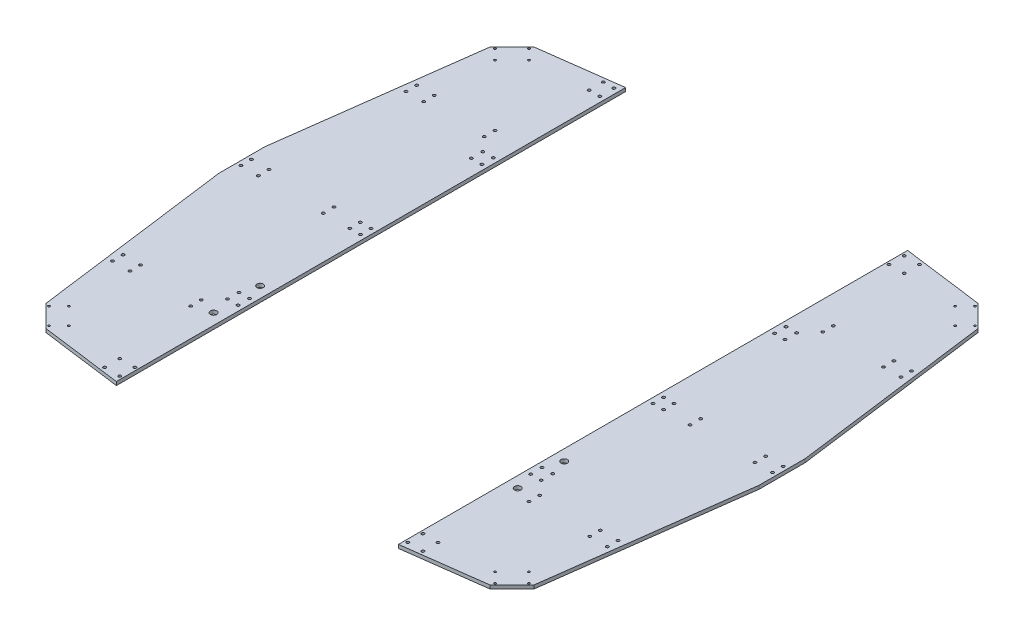
SolidWorks part; units mm, degrees
ref_plane "前视基准面" through (0, 0, 0) normal (0, 0, 1) x (1, 0, 0)
ref_plane "上视基准面" through (0, 0, 0) normal (0, 1, 0) x (1, 0, 0)
ref_plane "右视基准面" through (0, 0, 0) normal (1, 0, 0) x (0, 0, -1)
other "Configuration Table"
sketch "草图1" plane through (0, 0, 0) normal (0, 1, 0) x (1, 0, 0)
  line L0 (-314.9222, 345.9222) -> (-345.9222, 314.9222)
  line L5 (325, -325) -> (-325, 325) construction
  line L6 (325, 325) -> (-325, -325) construction
  line L7 (0, 325) -> (0, -325) construction
  line L8 (-383.07, 0) -> (383.0748, 0) construction
  line L9 (314.9222, 345.9222) -> (32.7201, 383.0748)
  line L10 (314.9222, 345.9222) -> (345.9222, 314.9222)
  line L11 (-383.07, 13.0001) -> (-230, 13.0001) construction
  line L12 (-314.9222, 345.9222) -> (-32.7201, 383.0748)
  line L13 (0, 325) -> (0, 399.6983)
  line L14 (-32.7201, 383.0748) -> (32.7201, 383.0748)
  line L15 (314.9222, -345.9222) -> (32.7201, -383.0748)
  line L16 (-32.7201, -383.0748) -> (32.7201, -383.0748)
  line L17 (-314.9222, -345.9222) -> (-32.7201, -383.0748)
  line L18 (-314.9222, -345.9222) -> (-345.9222, -314.9222)
  line L19 (-345.9222, 314.9222) -> (-383.0748, 32.7201)
  line L20 (-383.0748, -32.7201) -> (-383.0748, 32.7201)
  line L21 (-345.9222, -314.9222) -> (-383.0748, -32.7201)
  line L22 (-345.9222, -314.9222) -> (-314.9222, -345.9222)
  line L23 (345.9222, -314.9222) -> (314.9222, -345.9222)
  line L24 (345.9222, -314.9222) -> (383.0748, -32.7201)
  line L25 (383.0748, 32.7201) -> (383.0748, -32.7201)
  line L26 (345.9222, 314.9222) -> (383.0748, 32.7201)
  line L27 (-383.07, -12.9999) -> (-230, -12.9999) construction
  line L29 (361.6863, 195.182) -> (230, 195.182) construction
  line L30 (358.2633, 221.182) -> (230, 221.182) construction
  line L31 (-358.2633, 221.182) -> (-230, 221.182) construction
  line L32 (-361.6863, 195.182) -> (-230, 195.182) construction
  line L33 (361.6863, -195.182) -> (230, -195.182) construction
  line L34 (358.2633, -221.182) -> (230, -221.182) construction
  line L35 (-361.6863, -195.182) -> (-230, -195.182) construction
  line L36 (-358.2633, -221.182) -> (-230, -221.182) construction
  line L37 (-228, -357.3657) -> (-228, 357.3618) construction
  line L38 (-202, -360.7887) -> (-202, 360.7847) construction
  line L39 (383.07, 13.0001) -> (230, 13.0001) construction
  circle A5 centre (0, 0) radius 250
  circle A6 centre (302.1379, 326.1795) radius 1.5
  circle A7 centre (316.28, 340.3217) radius 1.5
  circle A8 centre (340.3217, 316.28) radius 1.5
  circle A9 centre (326.1795, 302.1379) radius 1.5
  circle A10 centre (302.1379, -326.1795) radius 1.5
  circle A11 centre (316.28, -340.3217) radius 1.5
  circle A12 centre (326.1795, -302.1379) radius 1.5
  circle A13 centre (340.3217, -316.28) radius 1.5
  circle A14 centre (-326.1795, -302.1379) radius 1.5
  circle A15 centre (-340.3217, -316.28) radius 1.5
  circle A16 centre (-302.1379, -326.1795) radius 1.5
  circle A17 centre (-316.28, -340.3217) radius 1.5
  circle A18 centre (-302.1379, 326.1795) radius 1.5
  circle A19 centre (-316.28, 340.3217) radius 1.5
  circle A20 centre (-326.1795, 302.1379) radius 1.5
  circle A21 centre (-340.3217, 316.28) radius 1.5
  circle A22 centre (350.9184, 215.682) radius 2
  circle A23 centre (377.0748, 7.5001) radius 2
  circle A24 centre (350.9184, 200.682) radius 2
  circle A25 centre (325.9184, 215.682) radius 2
  circle A26 centre (325.9184, 200.682) radius 2
  circle A27 centre (377.0748, -7.5951) radius 2
  circle A28 centre (352.0748, 7.5001) radius 2
  circle A29 centre (352.0748, -7.5951) radius 2
  circle A30 centre (350.9184, -200.682) radius 2
  circle A31 centre (350.9184, -215.682) radius 2
  circle A32 centre (325.9184, -200.682) radius 2
  circle A33 centre (325.9184, -215.682) radius 2
  circle A34 centre (-350.9184, -200.682) radius 2
  circle A35 centre (-325.9184, -200.682) radius 2
  circle A36 centre (-350.9184, -215.682) radius 2
  circle A37 centre (-325.9184, -215.682) radius 2
  circle A38 centre (-377.0748, 7.5001) radius 2
  circle A39 centre (-352.0748, 7.5001) radius 2
  circle A40 centre (-377.0748, -7.4999) radius 2
  circle A41 centre (-352.0748, -7.4999) radius 2
  circle A42 centre (-350.9184, 215.682) radius 2
  circle A43 centre (-350.9184, 200.682) radius 2
  circle A44 centre (-325.9184, 215.682) radius 2
  circle A45 centre (-325.9184, 200.682) radius 2
  circle A46 centre (-222.5, -164.8255) radius 2
  circle A47 centre (-207.5, -164.8255) radius 2
  circle A48 centre (-222.5, -181.0301) radius 2
  circle A49 centre (-207.5, -181.0301) radius 2
  circle A50 centre (-222.5, 181.0301) radius 2
  circle A51 centre (-207.5, 164.8255) radius 2
  circle A52 centre (-222.5, 164.8255) radius 2
  circle A53 centre (-207.5, 181.0301) radius 2
  circle A54 centre (207.5, -164.8255) radius 2
  circle A55 centre (222.5, -164.8255) radius 2
  circle A56 centre (207.5, -181.0301) radius 2
  circle A57 centre (222.5, -181.0301) radius 2
  circle A58 centre (207.5, 164.8255) radius 2
  circle A59 centre (222.5, 164.8255) radius 2
  circle A60 centre (207.5, 181.0301) radius 2
  circle A61 centre (222.5, 181.0301) radius 2
  circle A62 centre (-240, 215.682) radius 2
  circle A63 centre (-240, 200.682) radius 2
  circle A64 centre (-260, 7.5) radius 2
  circle A65 centre (-260, -7.5) radius 2
  circle A66 centre (-240, -200.682) radius 2
  circle A67 centre (-240, -215.682) radius 2
  circle A68 centre (240, -215.682) radius 2
  circle A69 centre (240, -200.682) radius 2
  circle A72 centre (240, 200.682) radius 2
  circle A73 centre (240, 215.682) radius 2
  circle A74 centre (207.5, 9.4052) radius 2
  circle A75 centre (222.5, 9.4052) radius 2
  circle A76 centre (207.5, -5.5948) radius 2
  circle A77 centre (222.5, -5.5948) radius 2
  circle A78 centre (-222.5, -5.5948) radius 2
  circle A79 centre (-207.5, -5.5948) radius 2
  circle A80 centre (-222.5, 9.4052) radius 2
  circle A81 centre (-207.5, 9.4052) radius 2
  circle A82 centre (260, -7.5) radius 2
  circle A83 centre (260, 7.5) radius 2
  circle A84 centre (215.6127, -141.5543) radius 4.5
  circle A85 centre (215.6127, -207.5543) radius 4.5
  circle A86 centre (-215.6127, -207.5543) radius 4.5
  circle A87 centre (-215.6127, -141.5543) radius 4.5
  point P0 (0, 0)
  point P13 (0, 383.0748)
  point P24 (-330.4222, -330.4222)
  point P75 (0, 0)
  dimension "D6" = 25
  dimension "D7" = 15
  dimension "D8" = 500
  dimension "D5" = 4
  dimension "D13" = 6
  dimension "D14" = 6
  dimension "D15" = 6
  dimension "D16" = 6
  dimension "D17" = 25
  dimension "D20" = 8
  dimension "D21" = 25
  dimension "D23" = 8
  dimension "D28" = 5.5
  dimension "D29" = 5.5
  dimension "D30" = 5.5
  dimension "D31" = 5.5
  dimension "D32" = 5.5
  dimension "D33" = 5.5
  dimension "D35" = 5.5
  dimension "D37" = 5.5
  dimension "D1" = 650
  dimension "D2" = 650
  dimension "D3" = 31
  dimension "D4" = 142.5
  dimension "D9" = 5.5
  dimension "D10" = 5.5
  dimension "D11" = 25
  dimension "D12" = 25
  dimension "D22" = 25
  dimension "D24" = 25
  dimension "D25" = 25
  dimension "D26" = 25
  dimension "D27" = 5.5
  dimension "D34" = 5.5
  dimension "D36" = 5.5
  dimension "D38" = 7.5001
  dimension "D39" = 7.4999
  dimension "D40" = 7.5
  dimension "D41" = 7.5
extrude "凸台-拉伸2" add sketch "草图1" along normal blind 5 contours L26 L10 L9 L14 L12 L0 L19 L20 L21 L18 L17 L16 L15 L23 L24 L25 | A13 L22 | L22 | A13 L18 region at (-172.4069, 0, -353.7562)
sketch "草图2" plane through (0, 5, 0) normal (0, 1, 0) x (1, 0, 0)
  line L0 (0, 0) -> (-330.4222, -330.4222) construction
  line L1 (0, 383.0748) -> (0, -383.0748)
  line L2 (-32.7201, 383.0748) -> (32.7201, 383.0748) construction
  line L3 (-32.7201, -383.0748) -> (32.7201, -383.0748) construction
  line L4 (-200, 361.052) -> (-200, -361.052)
  line L5 (-314.9222, 345.9222) -> (-32.7201, 383.0748) construction
  line L6 (-314.9222, -345.9222) -> (-32.7201, -383.0748) construction
  line L7 (200, 361.052) -> (200, -361.052)
  line L8 (314.9222, 345.9222) -> (32.7201, 383.0748) construction
  line L9 (314.9222, -345.9222) -> (32.7201, -383.0748) construction
  line L10 (-200, 361.052) -> (-200, 484.7149)
  line L11 (-200, 484.7149) -> (200, 484.7149)
  line L12 (200, 484.7149) -> (200, 361.052)
  line L13 (-200, -361.052) -> (-200, -418.819)
  line L14 (-200, -418.819) -> (200, -418.819)
  line L15 (200, -418.819) -> (200, -361.052)
  dimension "D1" = 200
  dimension "D2" = 200
extrude "切除-拉伸1" cut sketch "草图2" against normal blind 122 and the other way through all contours L4 L1 | L7 L1 | L7 L1 | L4 L1 | L0 L4 region at (-190.1188, 5, -422.8834)
sketch "草图3" plane through (0, 0, 0) normal (0, -1, 0) x (-1, 0, 0)
  circle A0 centre (225.7527, -352.0225) radius 2
  circle A1 centre (204.2473, -352.0225) radius 2
  circle A2 centre (225.7527, -330.517) radius 2
  circle A3 centre (204.2473, -330.517) radius 2
extrude "切除-拉伸2" cut sketch "草图3" along normal through all and the other way blind 39 contours A0 | A1 | A2 | A3
sketch "草图4" plane through (0, 5, 0) normal (0, 1, 0) x (1, 0, 0)
  line L0 (-222.5, 352.0186) -> (-207.5, 352.0186)
  line L1 (-215, 352.0186) -> (-215, 337.3883)
  line L2 (-228, -357.3657) -> (-228, 357.3618) construction
  line L3 (-202, -360.7887) -> (-202, 360.7847) construction
  line L4 (-228, -357.3657) -> (-228, 357.3618)
  line L5 (-202, -360.7887) -> (-202, 360.7847)
  line L6 (-202, 337.3883) -> (-228, 337.3883)
  circle A0 centre (-222.5, 352.0186) radius 2
  circle A1 centre (-207.5, 352.0186) radius 2
  circle A2 centre (-222.5, 332.0186) radius 2
  circle A3 centre (-207.5, 332.0186) radius 2
  circle A4 centre (204.2473, 330.5131) radius 2
  circle A5 centre (225.7527, 330.5131) radius 2
  circle A6 centre (204.2473, 352.0186) radius 2
  circle A7 centre (225.7527, 352.0186) radius 2
  circle A8 centre (204.2473, -352.0225) radius 2
  circle A9 centre (225.7527, -352.0225) radius 2
  circle A10 centre (204.2473, -330.517) radius 2
  circle A11 centre (225.7527, -330.517) radius 2
  dimension "D1" = 4
  dimension "D2" = 15
  dimension "D3" = 20
extrude "切除-拉伸3" cut sketch "草图4" against normal through all and the other way blind 20 contours A8 | A9 | A11 | A4 | A6 | A5 | A7 | A1 | A0 | A2 | A3 | A10 region at (-207.5, 5, -353.962) region at (-224.4434, 5, -352.0186) region at (-222.5, 5, -332.0186) region at (-207.5, 5, -332.0186) region at (204.2473, 5, -330.5131) region at (225.7527, 5, -330.5131) region at (204.2473, 5, -352.0186) region at (225.7527, 5, -352.0186) region at (204.2473, 5, 352.0225) region at (225.7527, 5, 352.0225) region at (225.7527, 5, 330.517)
sketch "草图5" plane through (0, 5, 0) normal (0, 1, 0) x (1, 0, 0)
  line L0 (-200, 150) -> (-200, -150)
  line L1 (200, 150) -> (200, -150)
  line L2 (-260, 7.5) -> (-260, -7.5) construction
  line L3 (-260, -7.5) -> (-200, -7.5) construction
  line L4 (-200, -7.5) -> (-200, 7.5)
  line L5 (-200, 7.5) -> (-260, 7.5) construction
  line L6 (-228, -357.3657) -> (-228, 357.3618) construction
  line L7 (-202, -360.7887) -> (-202, 360.7847) construction
  line L8 (0, 250) -> (0, -250) construction
  line L9 (-200, 361.048) -> (-200, -361.052) construction
  circle A0 centre (0, 0) radius 250
  circle A1 centre (-222.5, 7.5) radius 2
  circle A2 centre (-207.5, 7.5) radius 2
  circle A3 centre (-222.5, -7.5) radius 2
  circle A4 centre (-207.5, -7.5) radius 2
  circle A5 centre (207.5, -7.5) radius 2
  circle A6 centre (222.5, -7.5) radius 2
  circle A7 centre (207.5, 7.5) radius 2
  circle A8 centre (222.5, 7.5) radius 2
  dimension "D1" = 5.5
  dimension "D2" = 5.5
  dimension "D3" = 5.5
  dimension "D4" = 5.5
extrude "凸台-拉伸3" add sketch "草图5" against normal blind 5 contours L0 | L1 A0 region at (-220.2076, 5, 0) region at (220.2076, 5, 0)
